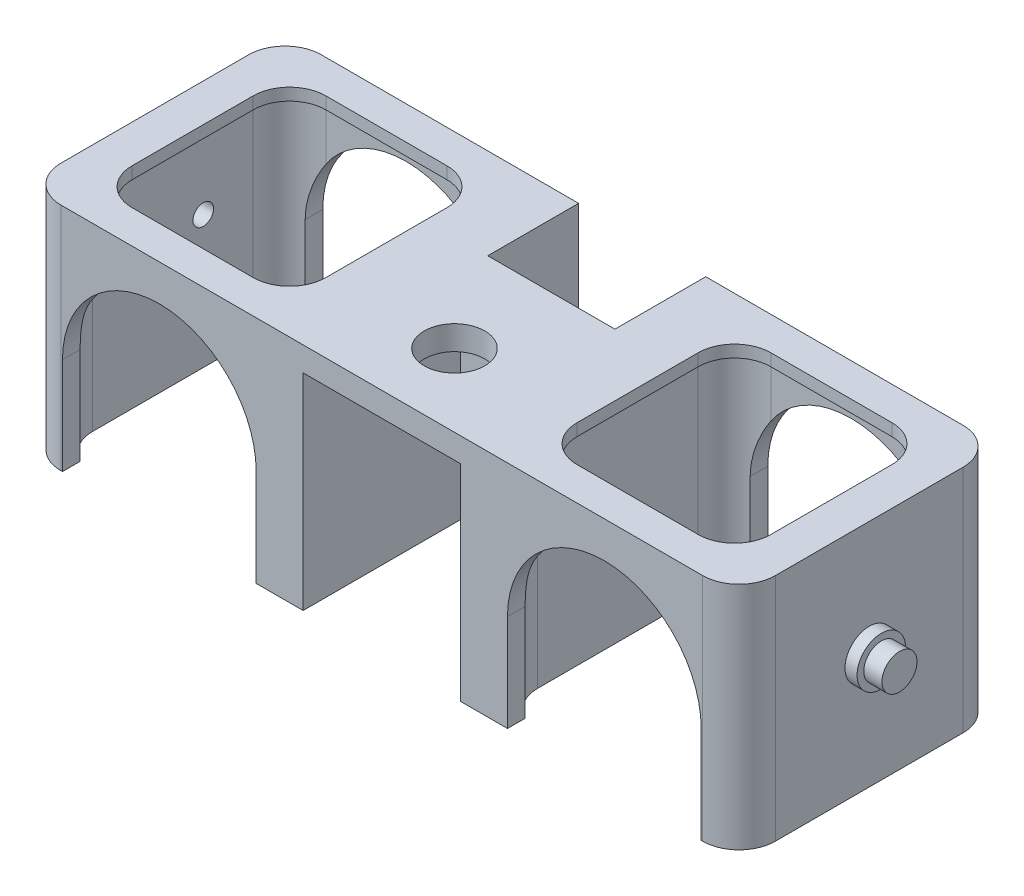
SolidWorks part; units mm, degrees
ref_plane "Front Plane" through (0, 0, 0) normal (0, 0, 1) x (1, 0, 0)
ref_plane "Top Plane" through (0, 0, 0) normal (0, 1, 0) x (1, 0, 0)
ref_plane "Right Plane" through (0, 0, 0) normal (1, 0, 0) x (0, 0, -1)
sketch "Sketch1" plane through (0, 0, 0) normal (0, 1, 0) x (1, 0, 0)
  line L1 (-59, -21.5) -> (59, -21.5)
  line L2 (-59, -21.5) -> (-59, 21.5)
  line L3 (-59, 21.5) -> (59, 21.5)
  line L4 (59, -21.5) -> (59, 21.5)
  line L5 (-59, -21.5) -> (59, 21.5) construction
  line L6 (-59, 21.5) -> (59, -21.5) construction
  point P0 (0, 0)
extrude "Boss-Extrude2" add sketch "Sketch1" along normal blind 38
sketch "Sketch2" plane through (0, 0, 0) normal (0, -1, 0) x (-1, 0, 0)
  line L0 (-59, 0) -> (-56, 0) construction
  line L1 (-59, -21.5) -> (-59, 21.5) construction
  line L2 (-17.5, -19.25) -> (-56, -19.25)
  line L3 (-17.5, -19.25) -> (-17.5, 19.25)
  line L4 (-56, -19.25) -> (-56, 19.25)
  line L5 (-17.5, 19.25) -> (-56, 19.25)
  line L6 (-17.5, -19.25) -> (-56, 19.25) construction
  line L7 (-56, -19.25) -> (-17.5, 19.25) construction
  line L8 (-56, 0) -> (-36.75, 0) construction
  line L11 (0, 21.5) -> (0, -21.5) construction
  line L12 (-59, 21.5) -> (59, 21.5) construction
  line L13 (59, -21.5) -> (-59, -21.5) construction
  line L14 (56, -19.25) -> (56, 19.25)
  line L15 (17.5, 19.25) -> (56, 19.25)
  line L16 (17.5, -19.25) -> (17.5, 19.25)
  line L17 (17.5, -19.25) -> (56, -19.25)
  point P6 (-36.75, 0)
extrude "Cut-Extrude1" cut sketch "Sketch2" against normal offset from surface (36 mm away) 2 up to face at (0, 38, 0)
sketch "Sketch3" plane through (0, 36, 0) normal (0, -1, 0) x (-1, 0, 0)
  line L0 (0, 0) -> (0, -15.6888) construction
  line L1 (-52.75, 16) -> (-20.75, 16)
  line L2 (-52.75, 16) -> (-52.75, -16)
  line L3 (-52.75, -16) -> (-20.75, -16)
  line L4 (-20.75, 16) -> (-20.75, -16)
  line L5 (-52.75, 16) -> (-20.75, -16) construction
  line L6 (-52.75, -16) -> (-20.75, 16) construction
  line L7 (52.75, 16) -> (52.75, -16)
  line L8 (52.75, -16) -> (20.75, -16)
  line L9 (20.75, 16) -> (20.75, -16)
  line L10 (52.75, 16) -> (20.75, 16)
  line L11 (-52.75, 0) -> (-59, 0) construction
  line L13 (-59, -21.5) -> (-59, 21.5) construction
  point P0 (-36.75, 0)
extrude "Cut-Extrude2" cut sketch "Sketch3" against normal up to surface (2 mm away) up to face at (0, 38, 0)
sketch "Sketch4" plane through (59, 0, 0) normal (1, 0, 0) x (0, 0, -1)
  line L0 (-21.5, 38) -> (21.5, 0) construction
  line L1 (0, 25.9282) -> (-6, 15.5359) construction
  line L2 (-6, 15.5359) -> (6, 15.5359) construction
  line L3 (6, 15.5359) -> (0, 25.9282) construction
  line L4 (-21.5, 0) -> (21.5, 38) construction
  circle A0 centre (0, 19) radius 3.4641 construction
  circle A4 centre (0, 19) radius 4
  point P15 (0, 19)
  dimension "D1" = 12
sketch "Sketch5" plane through (-59, 0, 0) normal (-1, 0, 0) x (0, 0, 1)
  line L0 (-21.5, 0) -> (21.5, 38) construction
  line L1 (-21.5, 38) -> (21.5, 0) construction
  line L3 (0, 13.2265) -> (5, 21.8868) construction
  line L4 (5, 21.8868) -> (-5, 21.8868) construction
  line L5 (-5, 21.8868) -> (0, 13.2265) construction
  circle A2 centre (0, 19) radius 2.8868 construction
  circle A3 centre (0, 13.2265) radius 1.7
  circle A4 centre (-5, 21.8868) radius 1.7
  circle A5 centre (5, 21.8868) radius 1.7
  point P8 (0, 19)
extrude "Cut-Extrude4" cut sketch "Sketch5" against normal up to surface (3 mm away) up to face at (-56, 18, 0)
sketch "Sketch14" plane through (0, 0, -21.5) normal (0, 0, -1) x (-1, 0, 0)
  line L0 (52.75, 0) -> (59, 0) construction
  line L8 (0, 0) -> (0, 38) construction
  line L14 (-59, 38) -> (59, 38) construction
  line L19 (-52.75, 0) -> (-20.75, 0)
  line L20 (52.75, 0) -> (20.75, 0)
  line L21 (52.75, 0) -> (52.75, 32)
  line L22 (52.75, 32) -> (20.75, 32)
  line L23 (20.75, 0) -> (20.75, 32)
  line L24 (-20.75, 0) -> (-20.75, 32)
  line L25 (-52.75, 32) -> (-20.75, 32)
  line L26 (-52.75, 0) -> (-52.75, 32)
extrude "Boss-Extrude3" add sketch "Sketch4" along normal blind 2
sketch "Sketch11" plane through (61, 0, 0) normal (1, 0, 0) x (0, 0, -1)
  circle A0 centre (0, 19) radius 2.9
extrude "Boss-Extrude4" add sketch "Sketch11" along normal blind 3
extrude "Cut-Extrude9" cut sketch "Sketch14" against normal up to surface (43 mm away) up to face at (0, 19, 21.5)
sketch "Sketch15" plane through (0, 38, 0) normal (0, 1, 0) x (1, 0, 0)
  line L0 (59, 21.5) -> (-59, 21.5) construction
  line L1 (10.5, 21.5) -> (-10.5, 21.5)
  line L2 (10.5, 21.5) -> (10.5, 6.5)
  line L3 (10.5, 6.5) -> (-10.5, 6.5)
  line L4 (-10.5, 21.5) -> (-10.5, 6.5)
  line L5 (0, 0) -> (0, 21.5) construction
  point P8 (0, 6.5)
extrude "Cut-Extrude10" cut sketch "Sketch15" against normal up to surface (38 mm away) contours L2 L1 L4 L3 up to face at (0, 0, 0)
fillet "Fillet2" radius 6 20 edges at (59, 19, -21.5) (-59, 19, -21.5) (-59, 19, 21.5) (59, 19, 21.5) (-17.5, 18, 19.25) (17.5, 18, 19.25) (-17.5, 18, -19.25) (17.5, 18, -19.25) (56, 18, 19.25) (56, 18, -19.25) (-56, 18, 19.25) (-56, 18, -19.25) (-52.75, 37, -16) (-52.75, 37, 16) (-20.75, 37, 16) (20.75, 37, -16) (20.75, 37, 16) (52.75, 37, 16) (52.75, 37, -16) (-20.75, 37, -16)
sketch "Sketch20" plane through (0, 0, 0) normal (0, -1, 0) x (1, 0, 0)
  line L0 (0, -6.5) -> (0, -18.5) construction
  line L1 (10.5, -6.5) -> (-10.5, -6.5) construction
  line L2 (-13.7, -18.5) -> (13.7, -18.5) construction
  circle A0 centre (13.7, -18.5) radius 1.5
  circle A1 centre (-13.7, -18.5) radius 1.5
  point P8 (0, -18.5)
extrude "Cut-Extrude15" cut sketch "Sketch20" against normal blind 26
sketch "Sketch18" plane through (0, 0, 0) normal (0, -1, 0) x (1, 0, 0)
  line L1 (-13, -4.5) -> (13, -4.5)
  line L2 (-13, -4.5) -> (-13, 21.5)
  line L3 (-13, 21.5) -> (13, 21.5)
  line L4 (13, -4.5) -> (13, 21.5)
  line L5 (-13, -4.5) -> (13, 21.5) construction
  line L6 (-13, 21.5) -> (13, -4.5) construction
  point P0 (0, 8.5)
extrude "Cut-Extrude13" cut sketch "Sketch18" against normal offset from surface (34 mm away) 4 contours L2 L1 L4 L3 up to face at (36.75, 38, 0)
sketch "Sketch19" plane through (0, 0, -4.5) normal (0, 0, 1) x (1, 0, 0)
  line L0 (-7, 18.2) -> (-7, 4) construction
  line L1 (-7, 11.1) -> (-13, 11.1) construction
  line L2 (-13, 34) -> (-13, 0) construction
  line L3 (-7, 4) -> (-7, 0) construction
  line L4 (-13, 0) -> (13, 0) construction
  line L5 (0, 0) -> (0, 34) construction
  line L6 (13, 34) -> (-13, 34) construction
  circle A0 centre (-7, 18.2) radius 1.5
  circle A1 centre (-7, 4) radius 1.5
  circle A2 centre (7, 18.2) radius 1.5
  circle A3 centre (7, 4) radius 1.5
extrude "Cut-Extrude14" cut sketch "Sketch19" against normal up to surface (2 mm away) up to face at (0, 19, -6.5)
sketch "Sketch21" plane through (0, 34, 0) normal (0, -1, 0) x (1, 0, 0)
  line L0 (13, -4.5) -> (-13, -4.5) construction
  line L1 (0, -4.5) -> (0, 9.5) construction
  circle A0 centre (0, 9.5) radius 5
extrude "Cut-Extrude16" cut sketch "Sketch21" against normal up to surface (4 mm away) up to face at (36.75, 38, 0)
fillet "Fillet3" radius 16 8 edges at (52.75, 32, -20.0413) (-20.75, 32, -20.0413) (-52.75, 32, -20.0413) (20.75, 32, -20.0413) (52.75, 32, 20.0413) (20.75, 32, 20.0413) (-20.75, 32, 20.0413) (-52.75, 32, 20.0413)
